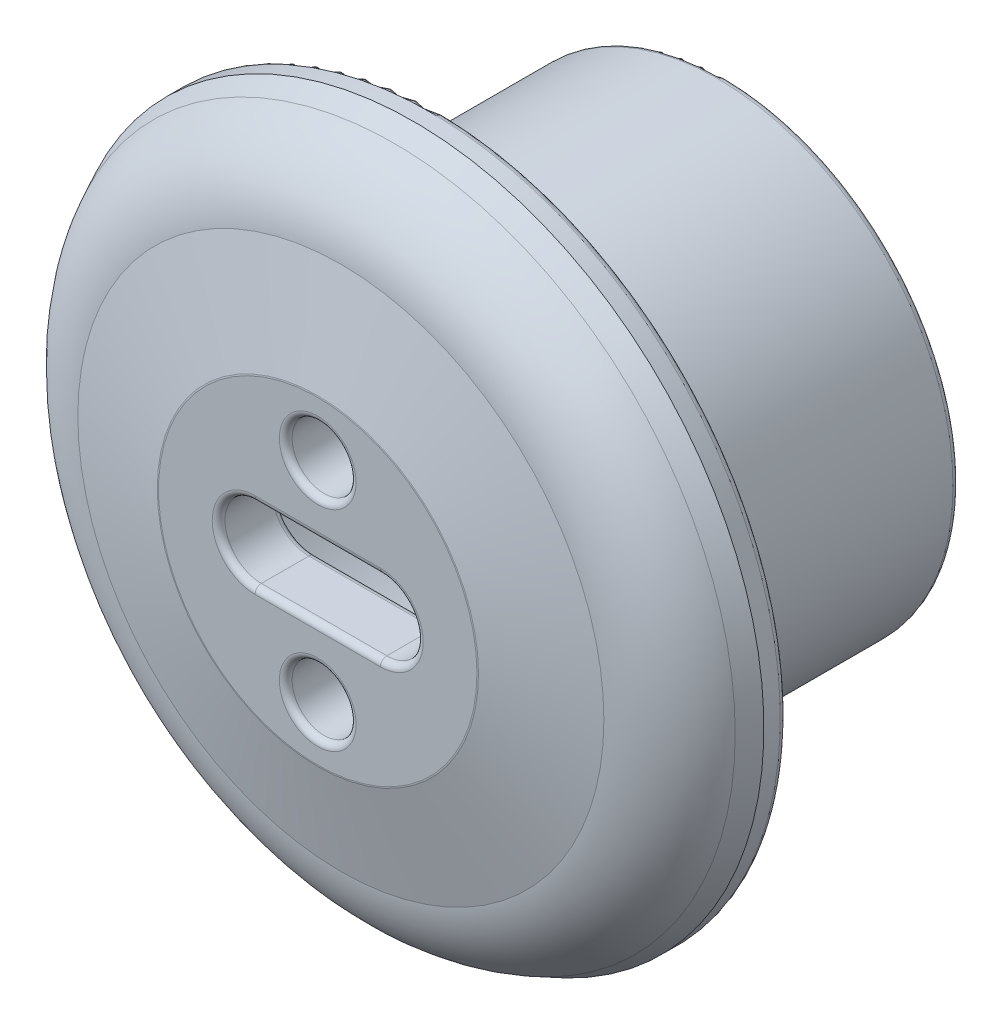
SolidWorks part; units mm, degrees
ref_plane "Front Plane" through (0, 0, 0) normal (0, 0, 1) x (1, 0, 0)
ref_plane "Top Plane" through (0, 0, 0) normal (0, 1, 0) x (1, 0, 0)
ref_plane "Right Plane" through (0, 0, 0) normal (1, 0, 0) x (0, 0, -1)
sketch "Sketch1" plane through (0, 0, 0) normal (1, 0, 0) x (0, 0, -1)
  line L0 (0, 0) -> (0, 10.95) construction
  line L1 (0, 10.95) -> (3, 10.95) construction
  line L3 (2.3972, 10.656) -> (3, 10.95)
  line L4 (3, 10.95) -> (3.7122, 10.95)
  line L5 (3.7122, 10.95) -> (3.7122, 8.9)
  line L6 (3.7122, 8.9) -> (4.7122, 8.9)
  line L7 (4.7122, 8.9) -> (4.7122, 7.35)
  line L8 (4.7122, 7.35) -> (12.7122, 7.35)
  line L11 (0, 0) -> (0, 5)
  line L12 (0, 5) -> (0.7238, 8.2226)
  line L13 (12.7122, 7.35) -> (12.7122, 6.35)
  line L14 (12.7122, 6.35) -> (3.2567, 6.35)
  line L18 (1.8825, 0) -> (0, 0)
  line L19 (3.2567, 6.35) -> (2.8825, 6.35)
  line L20 (1.8825, 5.35) -> (1.8825, 0)
  arc A0 (0.7238, 8.2226) -> (2.3972, 10.656) centre (3.7122, 7.9596) cw
  arc A1 (2.8825, 6.35) -> (1.8825, 5.35) centre (2.8825, 5.35) ccw
  dimension "D3" = 3
  dimension "D10" = 1
  dimension "D1" = 10.95
  dimension "D2" = 3
  dimension "D4" = 2.05
  dimension "D5" = 1
  dimension "D6" = 1.55
  dimension "D7" = 8
  dimension "D8" = 1
  dimension "D9" = 5
revolve "Revolve1" add sketch "Sketch1" angle 360 about L18
fillet "Fillet2" radius 0.2 4 edges at (-6.35, 0, -12.7122) (-10.95, 0, -3.7122) (-8.9, 0, -4.7122) (-7.35, 0, -12.7122)
sketch "Sketch2" plane through (0, 0, 0) normal (0, 0, 1) x (1, 0, 0)
  line L0 (-1.9596, 0) -> (1.9596, 0) construction
  line L1 (-1.9596, 1.1382) -> (1.9596, 1.1382)
  line L2 (-1.9596, -1.1382) -> (1.9596, -1.1382)
  line L3 (0, 0) -> (0, 3.2744) construction
  line L4 (0, 0) -> (6.2637, 0) construction
  line L5 (6.2637, 0) -> (-6.8437, 0) construction
  arc A0 (-1.9596, 1.1382) -> (-1.9596, -1.1382) centre (-1.9596, 0) ccw
  arc A1 (1.9596, -1.1382) -> (1.9596, 1.1382) centre (1.9596, 0) ccw
  circle A2 centre (0, 3.2744) radius 1
  circle A3 centre (0, -3.2744) radius 1
  point P2 (0, 0)
  dimension "D1" = 2
extrude "Cut-Extrude1" cut sketch "Sketch2" against normal blind 10
fillet "Fillet3" radius 0.2 13 edges at (0, 1.1382, -1.8825) (3.0978, 0, -1.8825) (0, -1.1382, -1.8825) (-3.0978, 0, -1.8825) (-1, 3.2744, -1.8825) (-1, -3.2744, -1.8825) (-5, 0, 0) (0, -1.1382, 0) (3.0978, 0, 0) (0, 1.1382, 0) (-3.0978, 0, 0) (1, 3.2744, 0) (-1, -3.2744, 0)
